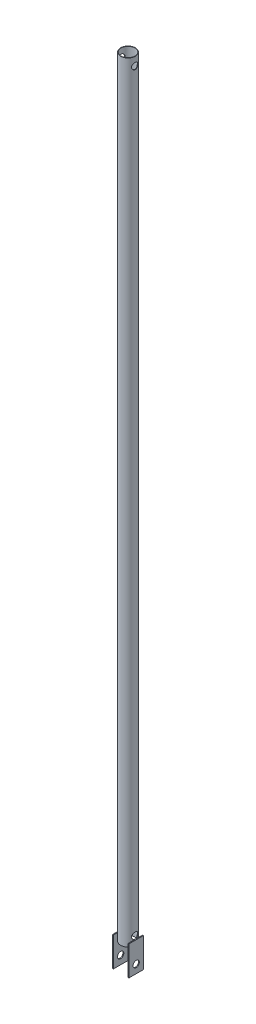
SolidWorks part; units mm, degrees
ref_plane "Front Plane" through (0, 0, 0) normal (0, 0, 1) x (1, 0, 0)
ref_plane "Top Plane" through (0, 0, 0) normal (0, 1, 0) x (1, 0, 0)
ref_plane "Right Plane" through (0, 0, 0) normal (1, 0, 0) x (0, 0, -1)
sketch "Sketch1" plane through (0, 0, 0) normal (0, 1, 0) x (1, 0, 0)
  circle A0 centre (0, 0) radius 17.46
  circle A1 centre (0, 0) radius 16.46
  dimension "D1" = 34.92
  dimension "D2" = 32.92
extrude "Boss-Extrude1" add sketch "Sketch1" along normal blind 1828.8
sketch "Sketch2" plane through (0, 0, 0) normal (1, 0, 0) x (0, 0, -1)
  line L0 (0, 1828.8) -> (0, 1788.8) construction
  line L1 (17.46, 1828.8) -> (-17.46, 1828.8) construction
  line L2 (16.46, 914.4) -> (-17.46, 914.4) construction
  line L3 (16.46, 0) -> (16.46, 1828.8) construction
  line L4 (-17.46, 1828.8) -> (-17.46, 0) construction
  line L5 (0, 0) -> (0, 40) construction
  circle A0 centre (0, 1808.8) radius 7.5
  circle A1 centre (0, 20) radius 7.5
  dimension "D2" = 15
  dimension "D1" = 40
extrude "Cut-Extrude1" cut sketch "Sketch2" against normal through all both and the other way through all contours A0 | A1
sketch "Sketch3" plane through (0, 0, 0) normal (0, 0, 1) x (1, 0, 0)
  line L0 (-17.46, 12.5) -> (-17.46, -57.5)
  line L1 (-17.46, 12.5) -> (-19.46, 12.5)
  line L2 (-19.46, 12.5) -> (-19.46, -57.5)
  line L3 (0, 0) -> (0, 22.9449) construction
  line L4 (-19.46, -57.5) -> (-17.46, -57.5)
  line L5 (17.46, 12.5) -> (17.46, -57.5)
  line L6 (17.46, 12.5) -> (19.46, 12.5)
  line L7 (19.46, 12.5) -> (19.46, -57.5)
  line L8 (19.46, -57.5) -> (17.46, -57.5)
  dimension "D1" = 70
  dimension "D2" = 2
extrude "Boss-Extrude2" add sketch "Sketch3" along normal blind 17.46 and the other way blind 17.46 separate body
sketch "Sketch4" plane through (19.46, 0, 0) normal (1, 0, 0) x (0, 0, -1)
  line L0 (0, -57.5) -> (0, -37.5) construction
  line L1 (17.46, -57.5) -> (-17.46, -57.5) construction
  circle A0 centre (0, -37.5) radius 7.5
  dimension "D2" = 15
  dimension "D1" = 20
extrude "Cut-Extrude2" cut sketch "Sketch4" against normal through all both
sketch "Sketch5" plane through (0, 0, 0) normal (0, 0, 1) x (1, 0, 0)
  point P5 (0, -37.5)
